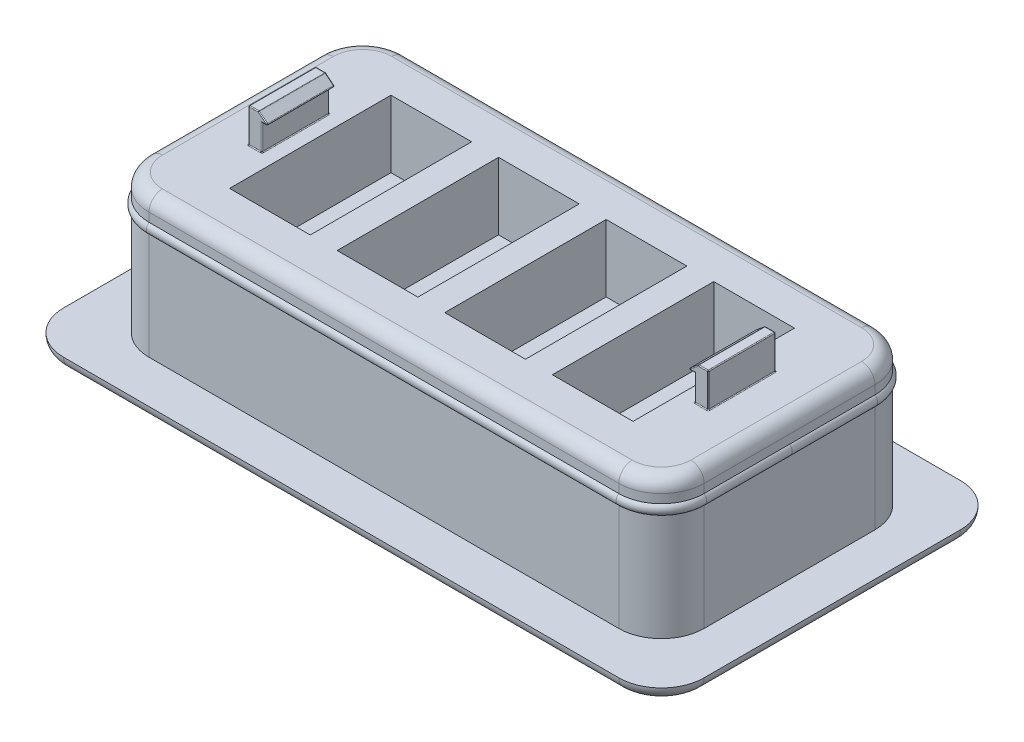
SolidWorks part; units mm, degrees
ref_plane "Front Plane" through (0, 0, 0) normal (0, 0, 1) x (1, 0, 0)
ref_plane "Top Plane" through (0, 0, 0) normal (0, 1, 0) x (1, 0, 0)
ref_plane "Right Plane" through (0, 0, 0) normal (1, 0, 0) x (0, 0, -1)
sketch "Sketch1" plane through (0, 0, 0) normal (0, 1, 0) x (1, 0, 0)
  line L1 (41.275, 19.05) -> (-41.275, 19.05)
  line L2 (41.275, 19.05) -> (41.275, -19.05)
  line L3 (41.275, -19.05) -> (-41.275, -19.05)
  line L4 (-41.275, 19.05) -> (-41.275, -19.05)
  line L5 (41.275, 19.05) -> (-41.275, -19.05) construction
  line L6 (41.275, -19.05) -> (-41.275, 19.05) construction
  point P0 (0, 0)
  dimension "D1" = 38.1
  dimension "D2" = 82.55
extrude "Boss-Extrude1" add sketch "Sketch1" along normal blind 12.7
sketch "Sketch2" plane through (0, 0, 0) normal (0, -1, 0) x (1, 0, 0)
  line L12 (-47.625, 25.4) -> (-47.625, -25.4)
  line L13 (-47.625, -25.4) -> (47.625, -25.4)
  line L14 (47.625, -25.4) -> (47.625, 25.4)
  line L15 (47.625, 25.4) -> (-47.625, 25.4)
  line L16 (-47.625, 25.4) -> (-47.625, -25.4)
  line L17 (-47.625, -25.4) -> (47.625, -25.4)
  line L18 (47.625, -25.4) -> (47.625, 25.4)
  line L19 (47.625, 25.4) -> (-47.625, 25.4)
  dimension "D1" = 6.35
extrude "Boss-Extrude2" add sketch "Sketch2" against normal blind 2
shell "Shell1" thickness 2 removed face at (0, 0, 0)
sketch "Sketch3" plane through (0, 10.7, 0) normal (0, -1, 0) x (1, 0, 0)
  line L0 (0, 0) -> (0, -17.05) construction
  line L1 (-27.175, 4.5339) -> (-20.825, 4.5339)
  line L2 (-27.175, 4.5339) -> (-27.175, -4.5339)
  line L3 (-27.175, -4.5339) -> (-20.825, -4.5339)
  line L4 (-20.825, 4.5339) -> (-20.825, -4.5339)
  line L5 (-27.175, 4.5339) -> (-20.825, -4.5339) construction
  line L6 (-27.175, -4.5339) -> (-20.825, 4.5339) construction
  line L7 (-11.175, 4.5339) -> (-4.825, 4.5339)
  line L8 (-11.175, 4.5339) -> (-11.175, -4.5339)
  line L9 (-11.175, -4.5339) -> (-4.825, -4.5339)
  line L10 (-4.825, 4.5339) -> (-4.825, -4.5339)
  line L11 (-11.175, 4.5339) -> (-4.825, -4.5339) construction
  line L12 (-11.175, -4.5339) -> (-4.825, 4.5339) construction
  line L13 (4.825, 4.5339) -> (11.175, 4.5339)
  line L14 (4.825, 4.5339) -> (4.825, -4.5339)
  line L15 (4.825, -4.5339) -> (11.175, -4.5339)
  line L16 (11.175, 4.5339) -> (11.175, -4.5339)
  line L17 (4.825, 4.5339) -> (11.175, -4.5339) construction
  line L18 (4.825, -4.5339) -> (11.175, 4.5339) construction
  line L19 (20.825, 4.5339) -> (27.175, 4.5339)
  line L20 (20.825, 4.5339) -> (20.825, -4.5339)
  line L21 (20.825, -4.5339) -> (27.175, -4.5339)
  line L22 (27.175, 4.5339) -> (27.175, -4.5339)
  line L23 (20.825, 4.5339) -> (27.175, -4.5339) construction
  line L24 (20.825, -4.5339) -> (27.175, 4.5339) construction
  line L25 (-39.275, -17.05) -> (39.275, -17.05) construction
  line L26 (-24, 0) -> (24, 0) construction
  point P0 (-24, 0)
  point P5 (-8, 0)
  point P10 (8, 0)
  point P15 (24, 0)
  dimension "D1" = 6.35
  dimension "D2" = 9.0678
  dimension "D3" = 16
  dimension "D4" = 16
extrude "Cut-Extrude1" cut sketch "Sketch3" against normal through all both and the other way through all
fillet "Fillet1" radius 6.35 12 edges at (-47.625, 1, 25.4) (-47.625, 1, -25.4) (47.625, 1, -25.4) (47.625, 1, 25.4) (-41.275, 7.35, -19.05) (41.275, 7.35, -19.05) (-41.275, 7.35, 19.05) (41.275, 7.35, 19.05) (-39.275, 5.35, 17.05) (39.275, 5.35, 17.05) (-39.275, 5.35, -17.05) (39.275, 5.35, -17.05)
fillet "Fillet2" radius 2 16 edges at (45.7651, 0, 23.5401) (47.625, 0, 0) (45.7651, 0, -23.5401) (0, 0, -25.4) (-45.7651, 0, -23.5401) (-47.625, 0, 0) (-45.7651, 0, 23.5401) (0, 0, 25.4) (39.275, 0, 0) (0, 0, 17.05) (-39.275, 0, 0) (0, 0, -17.05) (37.4151, 0, -15.1901) (37.4151, 0, 15.1901) (-37.4151, 0, 15.1901) (-37.4151, 0, -15.1901)
chamfer "Chamfer1" distance 2 angle 45 16 edges at (24, 10.7, 4.5339) (20.825, 10.7, 0) (24, 10.7, -4.5339) (27.175, 10.7, 0) (8, 10.7, 4.5339) (4.825, 10.7, 0) (8, 10.7, -4.5339) (11.175, 10.7, 0) (-8, 10.7, 4.5339) (-11.175, 10.7, 0) (-8, 10.7, -4.5339) (-4.825, 10.7, 0) (-24, 10.7, 4.5339) (-27.175, 10.7, 0) (-24, 10.7, -4.5339) (-20.825, 10.7, 0)
sketch "Sketch4" plane through (0, 12.7, 0) normal (0, 1, 0) x (1, 0, 0)
  line L0 (24, 4.5339) -> (24, -4.5339) construction
  line L7 (20.825, 4.5339) -> (27.175, 4.5339) construction
  line L8 (27.175, -4.5339) -> (20.825, -4.5339) construction
  line L9 (8, -4.5339) -> (8, 4.5339) construction
  line L10 (18, -12) -> (30, -12)
  line L11 (18, -12) -> (18, 12)
  line L12 (18, 12) -> (30, 12)
  line L13 (30, -12) -> (30, 12)
  line L14 (18, -12) -> (30, 12) construction
  line L15 (18, 12) -> (30, -12) construction
  line L16 (11.175, -4.5339) -> (4.825, -4.5339) construction
  line L17 (4.825, 4.5339) -> (11.175, 4.5339) construction
  line L18 (-8, -4.5339) -> (-8, 4.5339) construction
  line L19 (-4.825, -4.5339) -> (-11.175, -4.5339) construction
  line L20 (-11.175, 4.5339) -> (-4.825, 4.5339) construction
  line L21 (-24, -4.5339) -> (-24, 4.5339) construction
  line L22 (-20.825, -4.5339) -> (-27.175, -4.5339) construction
  line L23 (-27.175, 4.5339) -> (-20.825, 4.5339) construction
  line L25 (2, -12) -> (14, -12)
  line L26 (2, -12) -> (2, 12)
  line L27 (2, 12) -> (14, 12)
  line L28 (14, -12) -> (14, 12)
  line L29 (2, -12) -> (14, 12) construction
  line L30 (2, 12) -> (14, -12) construction
  line L31 (-14, -12) -> (-2, -12)
  line L32 (-14, -12) -> (-14, 12)
  line L33 (-14, 12) -> (-2, 12)
  line L34 (-2, -12) -> (-2, 12)
  line L35 (-14, -12) -> (-2, 12) construction
  line L36 (-14, 12) -> (-2, -12) construction
  line L37 (-30, -12) -> (-18, -12)
  line L38 (-30, -12) -> (-30, 12)
  line L39 (-30, 12) -> (-18, 12)
  line L40 (-18, -12) -> (-18, 12)
  line L41 (-30, -12) -> (-18, 12) construction
  line L42 (-30, 12) -> (-18, -12) construction
  line L44 (34.925, 19.05) -> (-34.925, 19.05)
  line L45 (-41.275, 12.7) -> (-41.275, -12.7)
  line L46 (-34.925, -19.05) -> (34.925, -19.05)
  line L47 (41.275, -12.7) -> (41.275, 12.7)
  line L48 (34.925, 19.05) -> (-34.925, 19.05)
  line L49 (-41.275, 12.7) -> (-41.275, -12.7)
  line L50 (-34.925, -19.05) -> (34.925, -19.05)
  line L51 (41.275, -12.7) -> (41.275, 12.7)
  arc A4 (-34.925, 19.05) -> (-41.275, 12.7) centre (-34.925, 12.7) ccw
  arc A5 (-41.275, -12.7) -> (-34.925, -19.05) centre (-34.925, -12.7) ccw
  arc A6 (34.925, -19.05) -> (41.275, -12.7) centre (34.925, -12.7) ccw
  arc A7 (41.275, 12.7) -> (34.925, 19.05) centre (34.925, 12.7) ccw
  arc A8 (-34.925, 19.05) -> (-41.275, 12.7) centre (-34.925, 12.7) ccw
  arc A9 (-41.275, -12.7) -> (-34.925, -19.05) centre (-34.925, -12.7) ccw
  arc A10 (34.925, -19.05) -> (41.275, -12.7) centre (34.925, -12.7) ccw
  arc A11 (41.275, 12.7) -> (34.925, 19.05) centre (34.925, 12.7) ccw
  point P0 (0, 0)
  point P12 (24, 0)
  point P35 (8, 0)
  point P40 (-8, 0)
  point P45 (-24, 0)
  dimension "D1" = 0
  dimension "D3" = 24
  dimension "D4" = 12
extrude "Boss-Extrude3" add sketch "Sketch4" along normal blind 9.98
sketch "Sketch5" plane through (0, 0, 0) normal (0, 0, 1) x (1, 0, 0)
  line L5 (41.275, 2) -> (41.275, 22.68) construction
  line L6 (47.625, 2) -> (41.275, 2) construction
  line L7 (41.275, 19.375) -> (41.275, 17.875)
  arc A0 (41.275, 19.375) -> (41.275, 17.875) centre (40.7273, 18.625) cw
  point P8 (41.656, 18.625)
  point P9 (0, 0)
  point P10 (41.275, 19.0623)
  dimension "D1" = 15.875
  dimension "D2" = 0.381
  dimension "D3" = 1.5
sketch "Sketch6" plane through (0, 22.68, 0) normal (0, 1, 0) x (1, 0, 0)
  line L4 (34.925, 19.05) -> (-34.925, 19.05)
  line L5 (-41.275, 12.7) -> (-41.275, -12.7)
  line L6 (-34.925, -19.05) -> (34.925, -19.05)
  line L7 (41.275, -12.7) -> (41.275, 12.7)
  line L8 (34.925, 19.05) -> (-34.925, 19.05)
  line L9 (-41.275, 12.7) -> (-41.275, -12.7)
  line L10 (-34.925, -19.05) -> (34.925, -19.05)
  line L11 (41.275, -12.7) -> (41.275, 12.7)
  arc A4 (41.275, 12.7) -> (34.925, 19.05) centre (34.925, 12.7) ccw
  arc A5 (-34.925, 19.05) -> (-41.275, 12.7) centre (-34.925, 12.7) ccw
  arc A6 (-41.275, -12.7) -> (-34.925, -19.05) centre (-34.925, -12.7) ccw
  arc A7 (34.925, -19.05) -> (41.275, -12.7) centre (34.925, -12.7) ccw
  arc A8 (41.275, 12.7) -> (34.925, 19.05) centre (34.925, 12.7) ccw
  arc A9 (-34.925, 19.05) -> (-41.275, 12.7) centre (-34.925, 12.7) ccw
  arc A10 (-41.275, -12.7) -> (-34.925, -19.05) centre (-34.925, -12.7) ccw
  arc A11 (34.925, -19.05) -> (41.275, -12.7) centre (34.925, -12.7) ccw
  dimension "D1" = 0
sweep "Sweep1" add profiles "Sketch5" path "Sketch6"
sketch "Sketch8" plane through (0, 0, 0) normal (0, 0, 1) x (1, 0, 0)
  line L0 (34.1798, 22.68) -> (34.1798, 27.76)
  line L2 (34.1798, 27.76) -> (32.6798, 27.76)
  line L3 (32.6798, 27.76) -> (31.1798, 26.535)
  line L4 (31.1798, 26.535) -> (32.1798, 26.535)
  line L5 (32.1798, 26.535) -> (32.1798, 22.68)
  line L6 (32.1798, 22.68) -> (34.1798, 22.68)
  line L7 (32, 24.77) -> (32, 26.37) construction
  line L8 (32, 26.37) -> (31.337, 26.37) construction
  line L9 (41.275, 2) -> (41.275, 17.875) construction
  line L10 (34.925, 22.68) -> (-34.925, 22.68) construction
  point P13 (0, 0)
  point P14 (0, 0)
  dimension "D1" = 2
  dimension "D2" = 5.08
  dimension "D3" = 0.165
  dimension "D4" = 0.1798
  dimension "D5" = 9.0952
  dimension "D6" = 3.855
  dimension "D7" = 1
  dimension "D8" = 1.5
extrude "Boss-Extrude4" add sketch "Sketch8" along normal mid plane 10
fillet "Fillet3" radius 0.125 17 edges at (32.1798, 22.68, 0) (32.1798, 24.6075, 5) (31.6798, 26.535, 5) (31.9298, 27.1475, 5) (33.1798, 22.68, 5) (34.1798, 22.68, 0) (34.1798, 25.22, 5) (34.1798, 25.22, -5) (31.9298, 27.1475, -5) (31.6798, 26.535, -5) (32.1798, 24.6075, -5) (33.1798, 22.68, -5) (34.1798, 27.76, 0) (33.4298, 27.76, 5) (32.6798, 27.76, 0) (33.4298, 27.76, -5) (31.1798, 26.535, 0)
mirror "Mirror1" about plane through (0, 0, 0) normal (1, 0, 0) of "Boss-Extrude4", "Fillet3"
fillet "Fillet4" radius 2 8 edges at (-39.4151, 22.68, 17.1901) (-41.275, 22.68, 0) (-39.4151, 22.68, -17.1901) (0, 22.68, -19.05) (39.4151, 22.68, -17.1901) (41.275, 22.68, 0) (39.4151, 22.68, 17.1901) (0, 22.68, 19.05)
